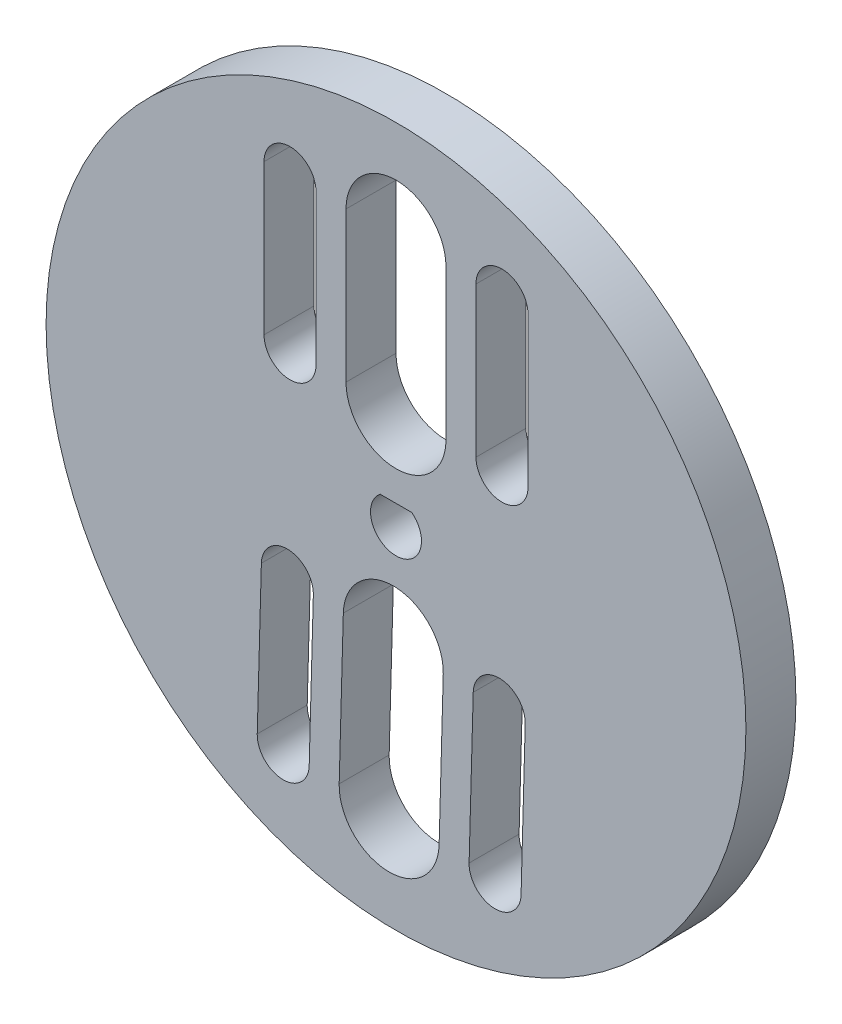
SolidWorks part; units mm, degrees
ref_plane "Plan de face" through (0, 0, 0) normal (0, 0, 1) x (1, 0, 0)
ref_plane "Plan de dessus" through (0, 0, 0) normal (0, 1, 0) x (1, 0, 0)
ref_plane "Plan de droite" through (0, 0, 0) normal (1, 0, 0) x (0, 0, -1)
sketch "Esquisse1" plane through (0, 0, 0) normal (0, 0, 1) x (1, 0, 0)
  line L0 (0, 0) -> (0, 35) construction
  line L1 (-5, 10) -> (5, 10)
  line L2 (-5, 10) -> (-5, 25)
  line L3 (-5, 25) -> (5, 25)
  line L4 (5, 10) -> (5, 25)
  line L5 (10.6, 25) -> (10.6, 10) construction
  line L6 (13.2, 25) -> (13.2, 10)
  line L7 (8, 25) -> (8, 10)
  line L8 (0, 10) -> (31.7532, 10) construction
  line L9 (-10.6, 25) -> (-10.6, 10) construction
  line L10 (-13.2, 25) -> (-13.2, 10)
  line L11 (-8, 25) -> (-8, 10)
  line L12 (4.7262, -10.4207) -> (4.3125, -25.415)
  line L13 (4.7262, -10.4207) -> (-5.27, -10.1449)
  line L14 (-5.27, -10.1449) -> (-5.6837, -25.1392)
  line L15 (4.3125, -25.415) -> (-5.6837, -25.1392)
  line L16 (12.5094, -25.6412) -> (12.9231, -10.6469)
  line L17 (7.3113, -25.4978) -> (7.7251, -10.5035)
  line L18 (-8.6826, -25.0564) -> (-8.2688, -10.0622)
  line L19 (-13.8806, -24.913) -> (-13.4669, -9.9187)
  line L20 (-11.2816, -24.9847) -> (-10.8679, -9.9904) construction
  line L21 (9.9103, -25.5695) -> (10.3241, -10.5752) construction
  circle A0 centre (0, 0) radius 35
  circle A1 centre (0, 25) radius 5
  circle A2 centre (0, 10) radius 5
  arc A3 (13.2, 25) -> (8, 25) centre (10.6, 25) ccw
  arc A4 (8, 10) -> (13.2, 10) centre (10.6, 10) ccw
  arc A5 (-13.2, 25) -> (-8, 25) centre (-10.6, 25) cw
  arc A6 (-8, 10) -> (-13.2, 10) centre (-10.6, 10) cw
  circle A7 centre (-0.2719, -10.2828) radius 5
  circle A8 centre (-0.6856, -25.2771) radius 5
  arc A9 (7.7251, -10.5035) -> (12.9231, -10.6469) centre (10.3241, -10.5752) cw
  arc A10 (12.5094, -25.6412) -> (7.3113, -25.4978) centre (9.9103, -25.5695) cw
  arc A11 (-13.8806, -24.913) -> (-8.6826, -25.0564) centre (-11.2816, -24.9847) ccw
  arc A12 (-8.2688, -10.0622) -> (-13.4669, -9.9187) centre (-10.8679, -9.9904) ccw
  point P13 (10.6, 17.5)
  point P22 (-10.6, 17.5)
  point P40 (-11.0747, -17.4876)
  point P47 (10.1172, -18.0723)
  point P52 (0.0039, -0.1433)
  dimension "D1" = 70
  dimension "D2" = 10
  dimension "D3" = 10
  dimension "D7" = 2.6
  dimension "D8" = 15
  dimension "D4" = 10
  dimension "D5" = 25
  dimension "D6" = 3
  dimension "D9" = 2
extrude "Boss.-Extru.1" add sketch "Esquisse1" along normal blind 5 contours A0 A12 L18 A11 L19 A8 L14 A7 L12 A4 L7 A3 L6 A2 L2 A1 L4 L11 A6 L10 A5 L16 A10 L17 A9 region at (0.0683, 0.0399, 0)
sketch "Esquisse2" plane through (0, 0, 5) normal (0, 0, 1) x (1, 0, 0)
  line L0 (-1.5819, 2) -> (1.5819, 2)
  line L7 (0, 2) -> (0, 2.55) construction
  circle A0 centre (0, 0) radius 2.55
  point P4 (0, 0)
  dimension "D1" = 5.1
  dimension "D2" = 0.55
extrude "Enlèv. mat.-Extru.1" cut sketch "Esquisse2" against normal up to next contours L0 A0 region at (0, -0.1372, 5)
